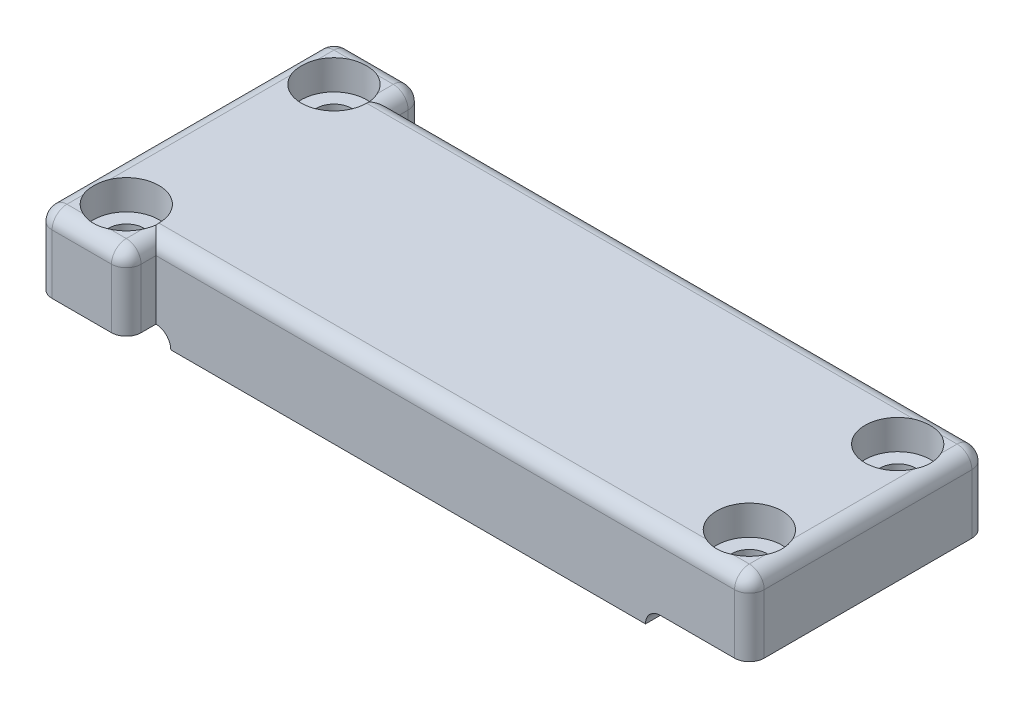
SolidWorks part; units mm, degrees
material "ABS PC"
ref_plane "前基準面" through (0, 0, 0) normal (0, 0, 1) x (1, 0, 0)
ref_plane "上基準面" through (0, 0, 0) normal (0, 1, 0) x (1, 0, 0)
ref_plane "右基準面" through (0, 0, 0) normal (1, 0, 0) x (0, 0, -1)
sketch "草圖1" plane through (0, 0, 0) normal (0, 1, 0) x (1, 0, 0)
  line L0 (0, 0) -> (-20, 0) construction
  line L1 (-20, -8) -> (20, -8)
  line L2 (-20, -4) -> (-20, 4)
  line L3 (-20, 8) -> (20, 8)
  line L4 (20, -8) -> (20, 8)
  line L5 (-20, 4) -> (-26, 4)
  line L6 (-26, 4) -> (-26, 10)
  line L7 (-26, 10) -> (-20, 10)
  line L8 (-20, 10) -> (-20, 8)
  line L9 (-20, -10) -> (-20, -8)
  line L10 (-26, -10) -> (-20, -10)
  line L11 (-26, -4) -> (-26, -10)
  line L12 (-20, -4) -> (-26, -4)
  dimension "D1" = 16
  dimension "D2" = 6
  dimension "D3" = 20
  dimension "D4" = 40
  dimension "D5" = 8
  dimension "D6" = 6
extrude "填料-伸長1" add sketch "草圖1" along normal blind 6
sketch "草圖2" plane through (0, 0, 0) normal (0, 1, 0) x (1, 0, 0)
  line L1 (-26, 4) -> (-20, 4)
  line L2 (-26, 4) -> (-26, -4)
  line L3 (-26, -4) -> (-20, -4)
  line L4 (-20, 4) -> (-20, -4)
extrude "填料-伸長2" add sketch "草圖2" along normal blind 4 from offset 2
fillet "圓角7" radius 1 1 edges at (-20, 2, 0)
sketch "草圖3" plane through (0, 0, 0) normal (0, -1, 0) x (-1, 0, 0)
  line L4 (-20, 8) -> (-13, 8)
  line L5 (-20, 8) -> (-20, -8)
  line L6 (-20, -8) -> (-13, -8)
  line L7 (-13, 8) -> (-13, -8)
  dimension "D1" = 7
  dimension "D2" = 16
extrude "除料-伸長1" cut sketch "草圖3" against normal blind 1
sketch "草圖4" plane through (0, 0, 0) normal (0, 1, 0) x (1, 0, 0)
  line L0 (-20, 0) -> (0, 0) construction
  circle A0 centre (-23, 7) radius 2.2
  circle A1 centre (-23, -7) radius 2.2
  circle A2 centre (17, 5) radius 2.2
  circle A3 centre (17, -5) radius 2.2
extrude "除料-伸長2" cut sketch "草圖4" along normal blind 2 from offset 4
sketch "草圖5" plane through (0, 4, 0) normal (0, 1, 0) x (1, 0, 0)
  circle A0 centre (-23, 7) radius 1.2
  circle A1 centre (-23, -7) radius 1.2
  circle A2 centre (17, 5) radius 1.2
  circle A3 centre (17, -5) radius 1.2
  dimension "D1" = 14
  dimension "D2" = 10
extrude "除料-伸長3" cut sketch "草圖5" against normal blind 3
fillet "圓角8" radius 1 2 edges at (0, 6, -8) (0, 6, 8)
fillet "圓角9" radius 1 5 edges at (20, 3, 8) (20, 5.7071, 7.7071) (20, 3, -8) (20, 5.7071, -7.7071) (20, 6, 0)
fillet "圓角10" radius 1 1 edges at (-20, 6, -8.5)
fillet "圓角11" radius 1 1 edges at (-20, 6, 8.5)
fillet "圓角12" radius 1 6 edges at (-23.5, 6, -10) (-20.2929, 5.7071, -10) (-23.5, 6, 10) (-20.2929, 5.7071, 10) (-20, 2.5, -10) (-20, 2.5, 10)
fillet "圓角13" radius 1 5 edges at (-26, 5.7071, 9.7071) (-26, 6, 0) (-26, 5.7071, -9.7071) (-26, 2.5, 10) (-26, 2.5, -10)
sketch "草圖6" plane through (0, 0, 0) normal (0, 1, 0) x (1, 0, 0)
  line L1 (-20, -10) -> (-26, -10)
  line L2 (-20, -10) -> (-20, 10)
  line L3 (-20, 10) -> (-26, 10)
  line L4 (-26, -10) -> (-26, 10)
extrude "除料-伸長4" cut sketch "草圖6" along normal blind 1
sketch "草圖7" plane through (0, 0, 0) normal (0, 1, 0) x (1, 0, 0)
  line L0 (-20, 8) -> (20, 8) construction
  line L1 (-20, -8) -> (-19, -8)
  line L2 (-20, -8) -> (-20, 8)
  line L3 (-20, 8) -> (-19, 8)
  line L4 (-19, -8) -> (-19, 8)
  dimension "D1" = 1
extrude "除料-伸長5" cut sketch "草圖7" along normal blind 1
fillet "圓角23" radius 1 1 edges at (-19, 1, 0)
fillet "圓角24" radius 1 1 edges at (13, 1, 0)
